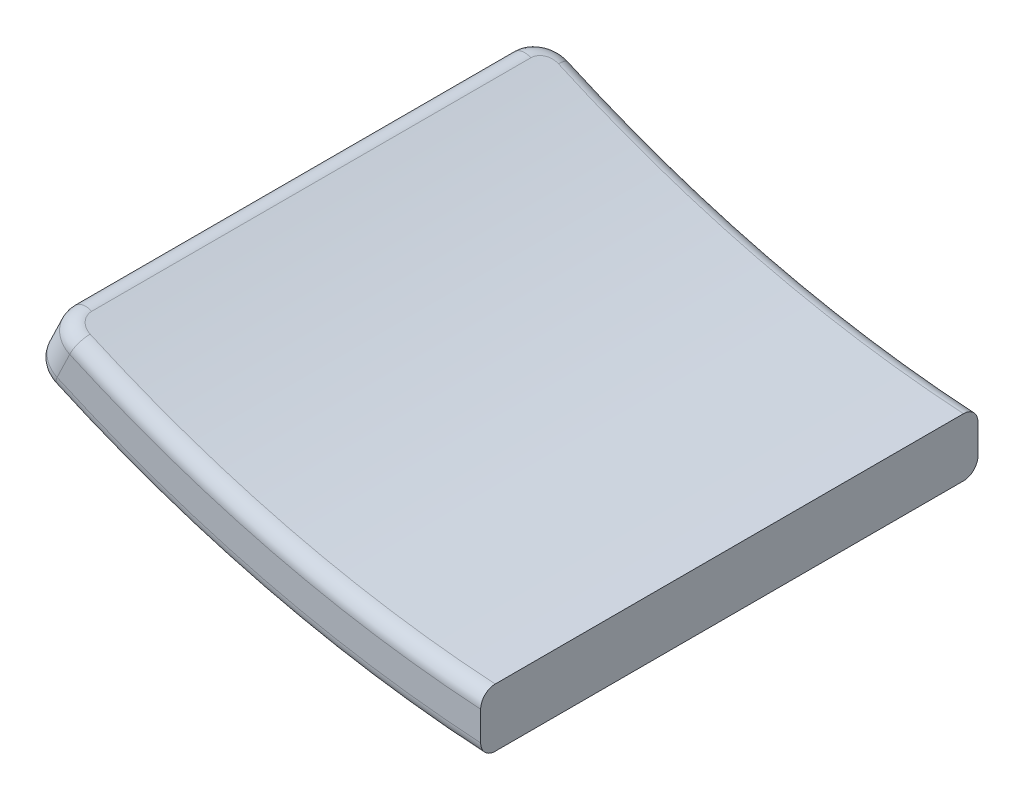
SolidWorks part; units mm, degrees
material "Polyurethane Foam Flexible"
ref_plane "Front Plane" through (0, 0, 0) normal (0, 0, 1) x (1, 0, 0)
ref_plane "Top Plane" through (0, 0, 0) normal (0, 1, 0) x (1, 0, 0)
ref_plane "Right Plane" through (0, 0, 0) normal (1, 0, 0) x (0, 0, -1)
sketch "Sketch1" plane through (0, 0, 0) normal (0, 0, 1) x (1, 0, 0)
  line L0 (-50.8051, 197.3186) -> (-50.8, 146.4209)
  line L1 (-427.4709, 295.7304) -> (-449.4633, 249.9377)
  line L2 (-50.8, -204.8629) -> (-50.8, 160.2621) construction
  arc A0 (-427.4709, 295.7304) -> (-0.043, 195.3653) centre (13.752, 1214.4469) ccw construction
  arc A1 (-427.4709, 295.7304) -> (-50.8051, 197.3186) centre (13.752, 1214.4469) ccw
  arc A2 (-449.4633, 249.9377) -> (-50.8, 146.4209) centre (13.752, 1214.4469) ccw
  arc A3 (-449.4633, 249.9377) -> (-0.7306, 144.57) centre (13.752, 1214.4469) ccw construction
  arc A4 (-427.4709, 295.7304) -> (-0.043, 195.3653) centre (13.752, 1214.4469) ccw construction
  dimension "D2" = 50.8
extrude "Boss-Extrude1" add sketch "Sketch1" against normal up to surface (434.6 mm away)
fillet "Fillet1" radius 25.4 2 edges at (-438.4671, 272.8341, 0) (-438.4671, 272.8341, -434.6)
fillet "Fillet2" radius 12.7 10 edges at (-242.8475, 175.6962, -434.6) (-444.4398, 247.5412, -425.0671) (-449.4633, 249.9377, -217.3) (-440.85, 245.8482, -5.5643) (-242.8475, 175.6962, 0) (-418.8565, 291.6428, -429.0358) (-231.5721, 225.2383, -434.6) (-231.5721, 225.2383, 0) (-422.4471, 293.3346, -9.5329) (-427.4709, 295.7304, -217.3)
